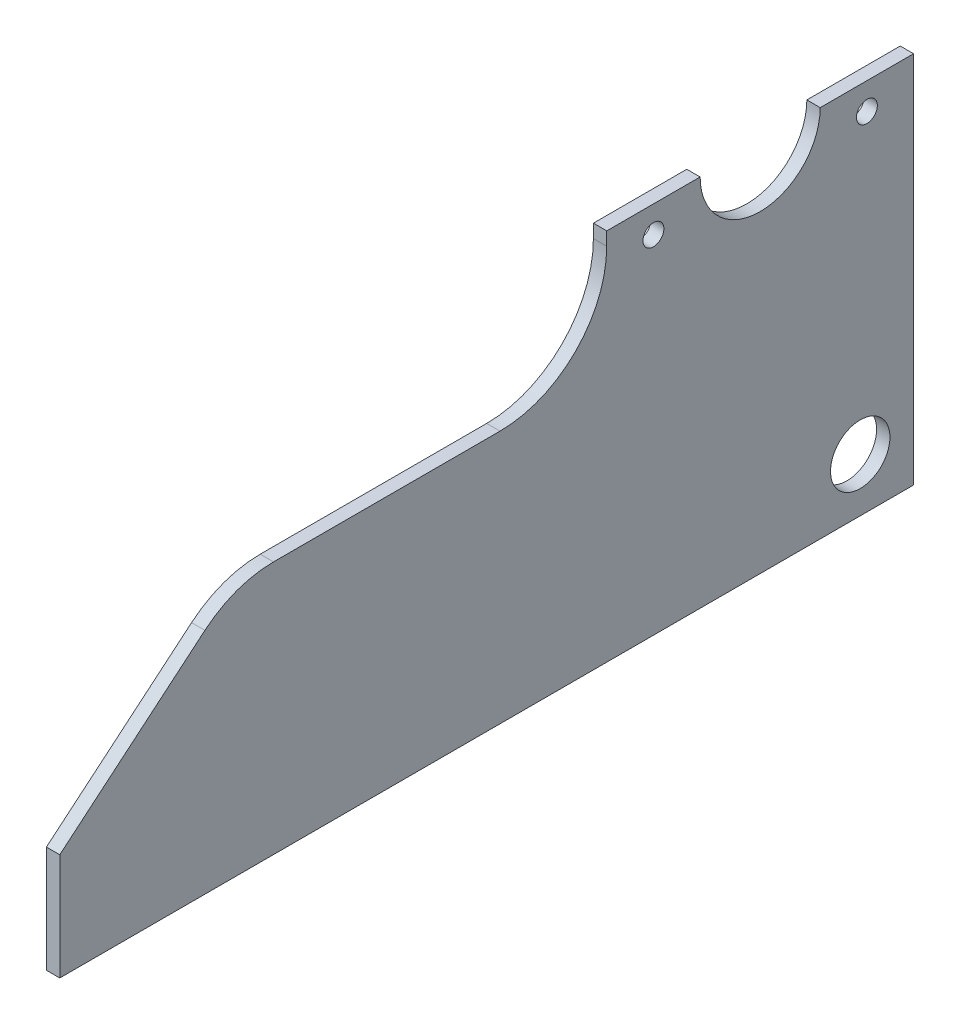
SolidWorks part; units mm, degrees
material "6061 Alloy"
ref_plane "Front Plane" through (0, 0, 0) normal (0, 0, 1) x (1, 0, 0)
ref_plane "Top Plane" through (0, 0, 0) normal (0, 1, 0) x (1, 0, 0)
ref_plane "Right Plane" through (0, 0, 0) normal (1, 0, 0) x (0, 0, -1)
sketch "Sketch1" plane through (0, 0, 0) normal (1, 0, 0) x (0, 0, -1)
  line L0 (0, -44.45) -> (0, 44.45)
  line L7 (0, 44.45) -> (-22.225, 44.45)
  line L8 (-50.8, 44.45) -> (-73.025, 44.45)
  line L10 (-98.425, 15.875) -> (-152.3332, 15.875)
  line L13 (-203.2, -44.45) -> (0, -44.45)
  line L14 (-203.2, -44.45) -> (-203.2, -19.05)
  line L15 (-203.2, -19.05) -> (-168.66, 9.9325)
  line L16 (-203.2, -19.05) -> (0, -19.05) construction
  line L18 (-73.025, 44.45) -> (-73.025, 41.275)
  arc A2 (-22.225, 44.45) -> (-50.8, 44.45) centre (-36.5125, 44.45) cw
  arc A4 (-152.3332, 15.875) -> (-168.66, 9.9325) centre (-152.3332, -9.525) ccw
  arc A6 (-73.025, 41.275) -> (-98.425, 15.875) centre (-98.425, 41.275) cw
  point P4 (0, 0)
  dimension "D1" = 28.575
  dimension "D4" = 25.4
  dimension "D7" = 25.4
  dimension "D2" = 88.9
  dimension "D3" = 73.025
  dimension "D5" = 3.175
  dimension "D6" = 203.2
  dimension "D8" = 50
extrude "Boss-Extrude1" add sketch "Sketch1" along normal blind 3.175
hole_wizard "#10 Clearance Hole1" positions "Sketch2" profile "Sketch3" hole size "#10" standard "ANSI Inch" end condition through all
sketch "Sketch2" plane through (3.175, 0, 0) normal (1, 0, 0) x (0, 0, -1)
  line L0 (-50.8, 44.45) -> (-73.025, 44.45) construction
  line L1 (-61.9125, 38.1) -> (-11.1125, 38.1) construction
  line L3 (-36.5125, 38.1) -> (-36.5125, 44.45) construction
  point P0 (-61.9125, 38.1)
  point P2 (-11.1125, 38.1)
  dimension "D1" = 50.8
  dimension "D2" = 6.35
sketch "Sketch3" plane through (3.175, 38.1, 61.9125) normal (0, 1, 0) x (0, 0, -1)
  line L0 (0, 0) -> (0, 3.175)
  line L1 (0, 3.175) -> (2.4892, 3.175)
  line L2 (2.4892, 3.175) -> (2.4892, 0)
  line L5 (2.4892, 0) -> (0, 0)
  line L11 (0, -6.35) -> (0, 107.95) construction
  dimension "Thru Hole Dia." = 4.9784
  dimension "Thru Hole Depth" = 3.175
sketch "Sketch9" plane through (3.175, 0, 0) normal (1, 0, 0) x (0, 0, -1)
  line L2 (0, -44.45) -> (0, 44.45) construction
  line L3 (-203.2, -44.45) -> (0, -44.45) construction
  circle A0 centre (-12.7, -31.75) radius 7.0739
  dimension "D1" = 14.1478
  dimension "D3" = 12.7
  dimension "D2" = 12.7
extrude "Cut-Extrude1" cut sketch "Sketch9" against normal through all
